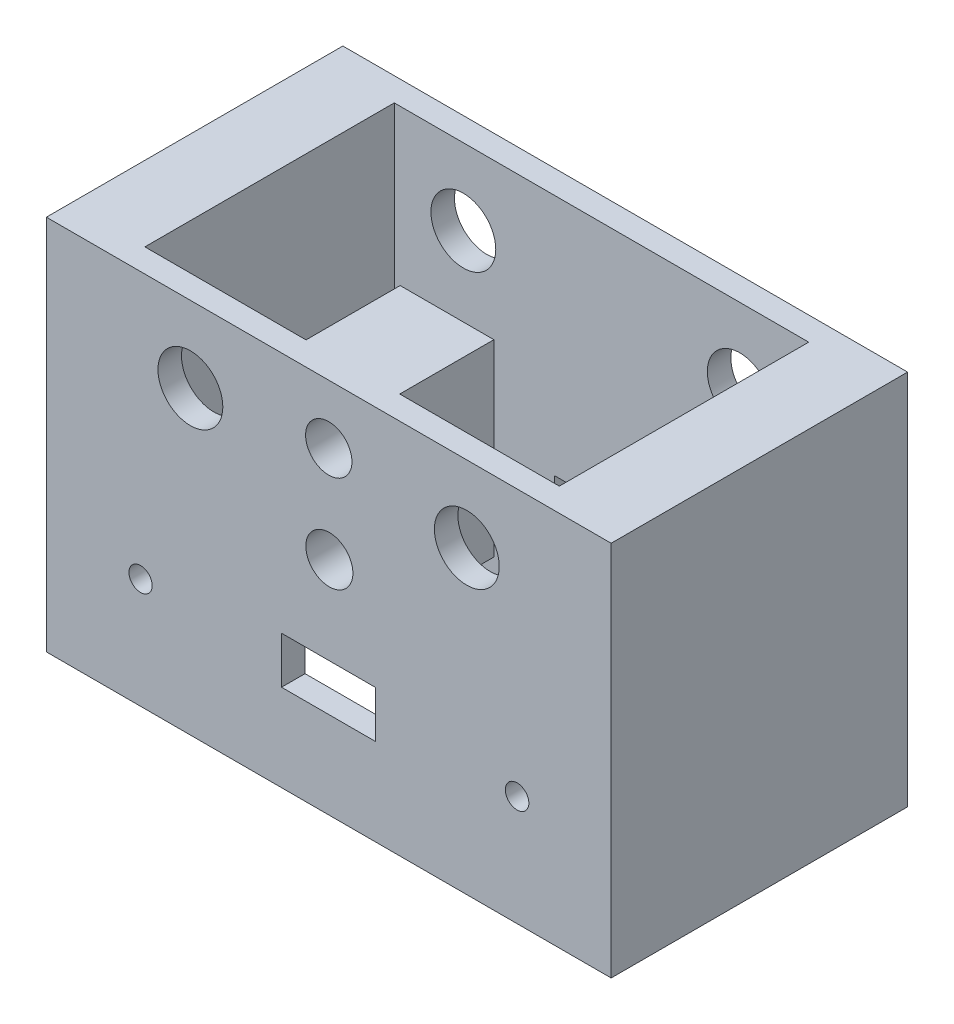
SolidWorks part; units mm, degrees
ref_plane "Front Plane" through (0, 0, 0) normal (0, 0, 1) x (1, 0, 0)
ref_plane "Top Plane" through (0, 0, 0) normal (0, 1, 0) x (1, 0, 0)
ref_plane "Right Plane" through (0, 0, 0) normal (1, 0, 0) x (0, 0, -1)
sketch "Sketch2" plane through (0, 0, 0) normal (0, 0, 1) x (1, 0, 0)
  line L0 (-38.9521, 81.0614) -> (0, 81.0614)
  line L1 (-152.4, 101.6) -> (0, 101.6)
  line L2 (-152.4, 101.6) -> (-152.4, 0)
  line L3 (-152.4, 0) -> (0, 0)
  line L4 (0, 101.6) -> (0, 0)
  line L9 (-113.538, 81.0614) -> (-152.4, 81.0614)
  line L10 (-76.1845, 9.2391) -> (-76.1845, 50.2517)
  line L11 (-130.1267, 29.7454) -> (-130.1267, 9.2391)
  line L12 (-22.2095, 29.7454) -> (-22.2095, 9.4254)
  line L13 (-48.8795, 29.7454) -> (-103.4895, 29.7454) construction
  line L14 (-48.8795, 9.4254) -> (-103.4895, 9.4254)
  line L15 (-48.8795, 50.0654) -> (-103.4895, 50.0654)
  line L17 (-22.2095, 29.7454) -> (-22.2095, 50.0654)
  line L19 (-130.1267, 9.2391) -> (-22.2095, 9.2391)
  line L20 (-130.1267, 9.2391) -> (-130.1267, 50.0654)
  line L21 (-130.1267, 50.0654) -> (-22.2095, 50.0654)
  line L22 (-22.2095, 9.2391) -> (-22.2095, 50.0654)
  line L23 (-88.9468, 29.7454) -> (-88.9468, 36.1065)
  line L24 (-88.9468, 36.1065) -> (-63.5515, 36.1065)
  line L25 (-63.5515, 36.1065) -> (-63.5515, 23.477)
  line L26 (-63.5515, 23.477) -> (-88.9468, 23.477)
  line L27 (-88.9468, 23.477) -> (-88.9468, 29.7454)
  circle A0 centre (-113.538, 81.0614) radius 8.75
  circle A1 centre (-38.9521, 81.0614) radius 8.75
  circle A2 centre (-25.3845, 29.7454) radius 3.175
  circle A3 centre (-126.9845, 29.7454) radius 3.1422
  arc A4 (-48.8795, 9.4254) -> (-48.8795, 50.0654) centre (-48.8795, 29.7454) ccw
  arc A5 (-103.4895, 50.0654) -> (-103.4895, 9.4254) centre (-103.4895, 29.7454) ccw
  point P26 (-76.1845, 29.7454)
  dimension "D5" = 17.5
  dimension "D6" = 17.5
  dimension "D10" = 6.35
  dimension "D11" = 20.32
  dimension "D3" = 6.2844
  dimension "D1" = 152.4
  dimension "D2" = 101.6
  dimension "D7" = 38.9521
  dimension "D8" = 38.862
  dimension "D12" = 54.61
extrude "Boss-Extrude1" add sketch "Sketch2" along normal blind 80.0001 contours A1 L4 L1 L2 A0 L3 L22 L19 L11 L20 L21 L15 L17 L12 | L15 A5 L14 L10 | A4 L15 L10 L14 | A5 L21 L20 A3 L11 L19 L10 L14 | A4 L14 L10 L19 L22 L12 A2 | A4 A2 L17 L21 region at (-76.2112, 58.2188, 0) region at (-103.1556, 9.3068, 0) region at (-29.741, 16.0891, 0) region at (-99.6175, 29.7407, 0) region at (-52.7624, 29.7408, 0) region at (-28.7715, 43.065, 0)
sketch "Sketch3" plane through (0, 101.6, 0) normal (0, 1, 0) x (1, 0, 0)
  line L0 (-76.2, 0) -> (-76.2, -6.35)
  line L1 (-152.4, 0) -> (0, 0) construction
  line L2 (-76.2, -80.0001) -> (-76.2, -73.6501)
  line L4 (-152.4, -80.0001) -> (0, -80.0001) construction
  line L9 (-76.2, -73.6501) -> (-132.171, -73.6501)
  line L10 (-76.2, -73.6501) -> (-20.3348, -73.6501)
  line L11 (-76.2, -6.35) -> (-132.171, -6.35)
  line L12 (-76.2, -6.35) -> (-20.3348, -6.35)
  line L13 (-132.171, -73.6501) -> (-132.171, -6.35)
  line L14 (-20.3348, -6.35) -> (-20.3348, -73.6501)
  dimension "D1" = 6.35
extrude "Cut-Extrude2" cut sketch "Sketch3" against normal blind 179.8221 contours L14 L12 L11 L13 L9 L10 region at (-76.2529, 101.6, 40)
sketch "Sketch6" plane through (0, 0, 73.6501) normal (0, 0, -1) x (-1, 0, 0)
  line L0 (76.2, 101.6) -> (63.3976, 101.6)
  line L1 (152.4, 101.6) -> (0, 101.6) construction
  line L2 (63.3976, 101.6) -> (63.3976, 50.8)
  line L3 (63.3976, 50.8) -> (88.685, 50.8)
  line L4 (88.685, 50.8) -> (88.685, 101.6)
  line L5 (88.685, 101.6) -> (76.2, 101.6)
  circle A0 centre (76.0413, 59.7405) radius 6.35
  circle A1 centre (76.2, 85.6628) radius 6.2488
  dimension "D1" = 50.8
extrude "Cut-Extrude6" cut sketch "Sketch6" against normal blind 41.402 contours A0 | A1 region at (-76.0413, 59.7405, 73.6501)
extrude "Boss-Extrude4" add sketch "Sketch6<10>" along normal blind 25.4
sketch "Sketch6<10>" plane through (0, 0, 73.6501) normal (0, 0, -1) x (-1, 0, 0) same geometry as "Sketch6"
